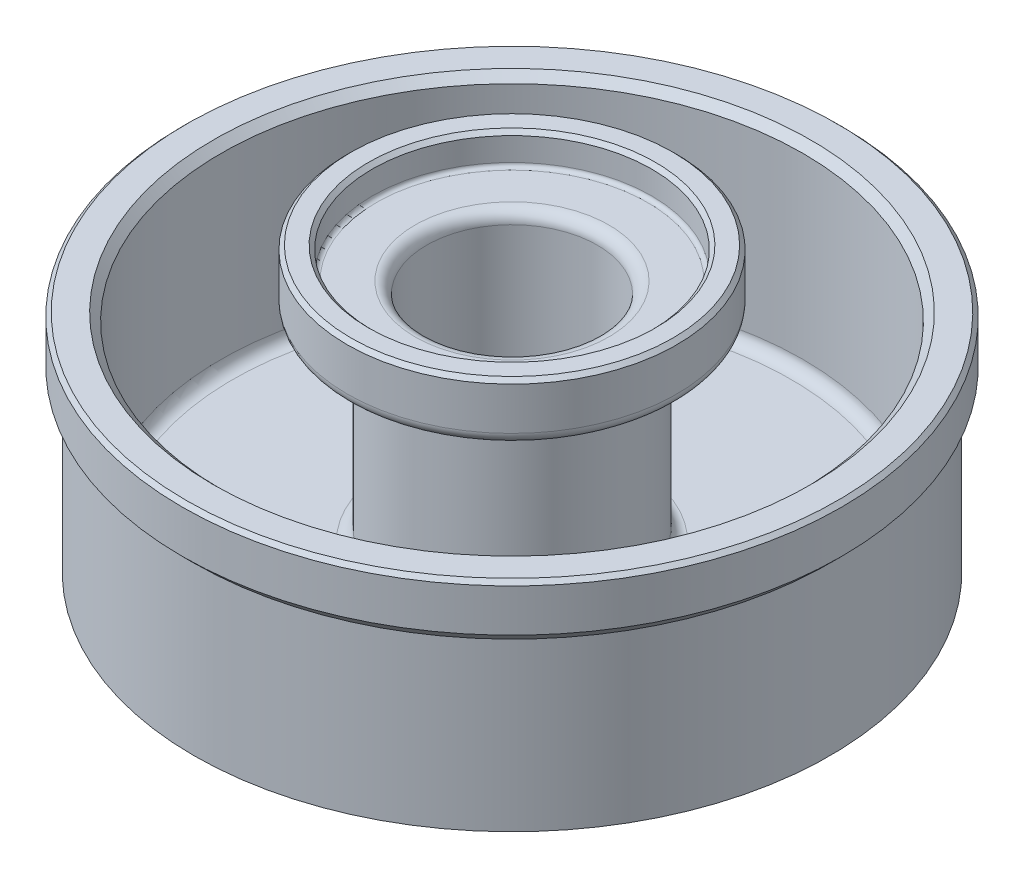
SolidWorks part; units mm, degrees
ref_plane "Front Plane" through (0, 0, 0) normal (0, 0, 1) x (1, 0, 0)
ref_plane "Top Plane" through (0, 0, 0) normal (0, 1, 0) x (1, 0, 0)
ref_plane "Right Plane" through (0, 0, 0) normal (1, 0, 0) x (0, 0, -1)
sketch "Sketch2" plane through (0, 0, 0) normal (0, 1, 0) x (1, 0, 0)
  circle A0 centre (0, 0) radius 82
  dimension "D1" = 164
extrude "Boss-Extrude1" add sketch "Sketch2" along normal blind 43
sketch "Sketch3" plane through (0, 43, 0) normal (0, 1, 0) x (1, 0, 0)
  circle A0 centre (0, 0) radius 85
extrude "Boss-Extrude2" add sketch "Sketch3" along normal blind 15
sketch "Sketch4" plane through (0, 58, 0) normal (0, 1, 0) x (1, 0, 0)
  circle A0 centre (0, 0) radius 75
  dimension "D1" = 150
extrude "Cut-Extrude1" cut sketch "Sketch4" against normal blind 51
sketch "Sketch5" plane through (0, 7, 0) normal (0, 1, 0) x (1, 0, 0)
  circle A0 centre (0, 0) radius 29
  dimension "D1" = 58
extrude "Boss-Extrude3" add sketch "Sketch5" along normal blind 51
sketch "Sketch6" plane through (0, 58, 0) normal (0, 1, 0) x (1, 0, 0)
  circle A0 centre (0, 0) radius 42.5
  dimension "D1" = 85
extrude "Boss-Extrude4" add sketch "Sketch6" along normal blind 15
sketch "Sketch7" plane through (0, 73, 0) normal (0, 1, 0) x (1, 0, 0)
  circle A0 centre (0, 0) radius 36
  circle A2 centre (0, 0) radius 22
  dimension "D1" = 72
  dimension "D2" = 44
extrude "Cut-Extrude6" cut sketch "Sketch7" against normal blind 8 contours A0
extrude "Cut-Extrude7" cut sketch "Sketch7<5>" against normal through all contours A2 region at (0, 73, 0)
sketch "Sketch7<5>" plane through (0, 73, 0) normal (0, 1, 0) x (1, 0, 0) same geometry as "Sketch7"
chamfer "Chamfer1" distance 1 angle 45 3 edges at (0, 58, 85) (0, 73, 42.5) (0, 73, 36)
chamfer "Chamfer2" distance 2 angle 45 1 edges at (0, 58, 75)
fillet "Fillet1" radius 3 6 edges at (0, 7, 29) (0, 58, 29) (0, 0, 22) (0, 65, 22) (0, 7, 75) (0, 58, 42.5)
chamfer "Chamfer3" distance 3 angle 45 1 edges at (0, 43, 85)
fillet "Fillet2" radius 1 1 edges at (0, 65, 36)
